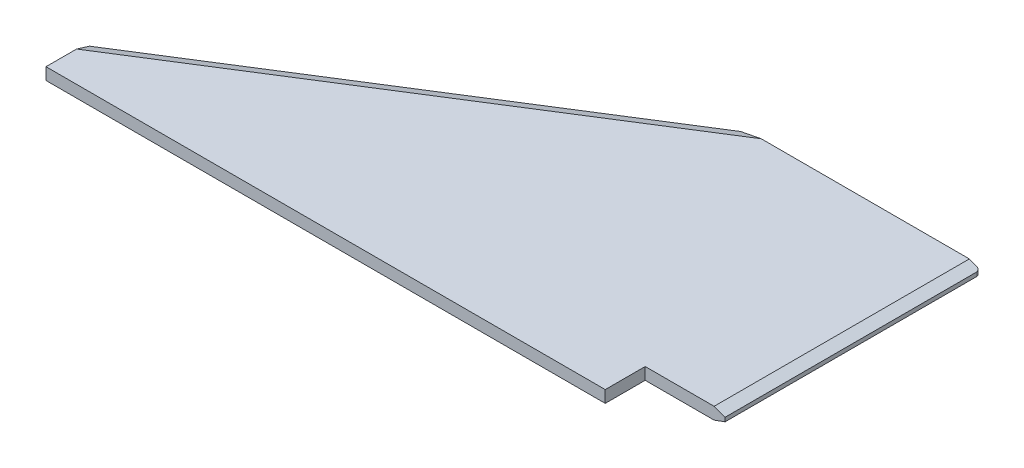
SolidWorks part; units mm, degrees
material "A-Glass Fiber"
ref_plane "Front Plane" through (0, 0, 0) normal (0, 0, 1) x (1, 0, 0)
ref_plane "Top Plane" through (0, 0, 0) normal (0, 1, 0) x (1, 0, 0)
ref_plane "Right Plane" through (0, 0, 0) normal (1, 0, 0) x (0, 0, -1)
sketch "Sketch1" plane through (0, 0, 0) normal (0, 1, 0) x (1, 0, 0)
  line L0 (0, 0) -> (0, 10.9)
  line L1 (0, 10.9) -> (100, 73.9)
  line L2 (100, 73.9) -> (160, 73.9)
  line L3 (160, 73.9) -> (160, 10.9)
  line L4 (160, 10.9) -> (160, 0)
  line L5 (160, 0) -> (152.5, 0)
  line L6 (152.5, 0) -> (152.5, 9.4) construction
  line L7 (152.5, 9.4) -> (149, 9.4) construction
  line L8 (149, 9.4) -> (149, 0) construction
  line L9 (149, 0) -> (0, 0)
  line L10 (-989.0676, -29) -> (49010.9324, -29) construction
  line L11 (-1000, 0) -> (49000, 0) construction
  line L12 (-999.3384, -58) -> (49000.6616, -58) construction
  line L13 (0, 0) -> (0, -58) construction
  line L14 (149, 0) -> (152.5, 0)
  point P15 (0, -29)
  dimension "D1" = 60
  dimension "D2" = 160
  dimension "D3" = 1.5
  dimension "D4" = 100
  dimension "D5" = 63
  dimension "D6" = 79.8
  dimension "D7" = 58
  dimension "D8" = 3.5
  dimension "D9" = 7.5
extrude "Boss-Extrude1" add sketch "Sketch1" along normal blind 3
chamfer "Chamfer1" distance 1 angle 70 2 edges at (160, 3, -36.95) (50, 3, -42.4) first distance on face at (160, 1.5, -36.95) first distance on face at (50, 1.5, -42.4)
chamfer "Chamfer2" distance 1 angle 70 2 edges at (50, 0, -42.4) (160, 0, -36.95) first distance on face at (50, 1, -42.4) first distance on face at (160, 1, -36.95)
fillet "Fillet1" radius 1 1 edges at (160, 1.5, -73.9)
sketch "Sketch2" plane through (0, 3, 0) normal (0, 1, 0) x (1, 0, 0)
  line L0 (0, 7.6527) -> (0, 0) construction
  line L1 (160, 0) -> (140, 0)
  line L2 (160, 0) -> (160, 10)
  line L3 (160, 10) -> (140, 10)
  line L4 (140, 0) -> (140, 10)
  dimension "D1" = 140
  dimension "D2" = 10
extrude "Cut-Extrude1" cut sketch "Sketch2" against normal blind 10
